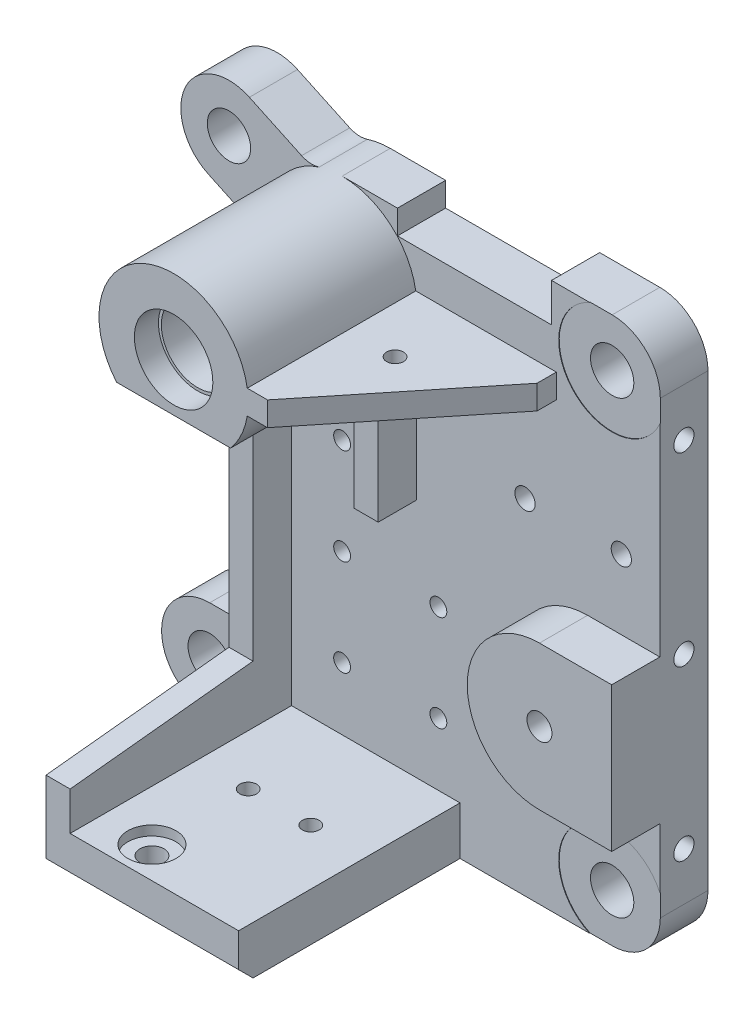
SolidWorks part; units mm, degrees
material "3D printed plastic"
ref_plane "Front Plane" through (0, 0, 0) normal (0, 0, 1) x (1, 0, 0)
ref_plane "Top Plane" through (0, 0, 0) normal (0, 1, 0) x (1, 0, 0)
ref_plane "Right Plane" through (0, 0, 0) normal (1, 0, 0) x (0, 0, -1)
sketch "Sketch1" plane through (0, 0, 0) normal (1, 0, 0) x (0, 0, -1)
  line L0 (0, 15.5) -> (-45, 15.5)
  line L1 (-45, 15.5) -> (-45, 8.15)
  line L2 (-45, 8.15) -> (-40, 8.15)
  line L3 (-40, 8.15) -> (-40, 7.55)
  line L4 (-40, 7.55) -> (-5, 7.55)
  line L5 (-5, 7.55) -> (-5, 8.15)
  line L6 (-5, 8.15) -> (0, 8.15)
  line L7 (0, 8.15) -> (0, 15.5)
  line L8 (0, 0) -> (-45, 0) construction
  dimension "D1" = 16.3
  dimension "D2" = 5
  dimension "D3" = 0.6
  dimension "D4" = 45
  dimension "D5" = 31
revolve "Revolve1" add sketch "Sketch1" angle 360 about L8
sketch "Sketch2" plane through (0, 0, 0) normal (0, 0, 1) x (1, 0, 0)
  line L0 (0, 15.5) -> (66, 15.5)
  line L1 (66, 15.5) -> (66, -95)
  line L2 (66, -95) -> (-15.5, -95)
  line L3 (-15.5, -95) -> (-15.5, 0)
  line L4 (0, 0) -> (0, -53) construction
  line L5 (0, -53) -> (51, -53) construction
  arc A0 (-15.5, 0) -> (0, 15.5) centre (0, 0) ccw
  circle A1 centre (0, 0) radius 15.5 construction
  dimension "D1" = 66
  dimension "D2" = 95
  dimension "D3" = 53
  dimension "D4" = 51
extrude "Boss-Extrude1" add sketch "Sketch2" along normal blind 10
ref_axis "Axis1" through (51, -53, 0) along (0, 0, 1)
sketch "Sketch3" plane through (0, 0, 10) normal (0, 0, 1) x (1, 0, 0)
  line L0 (51, -38) -> (66, -38)
  line L1 (66, -95) -> (66, 15.5) construction
  line L2 (66, -38) -> (66, -68)
  line L3 (66, -68) -> (51, -68)
  circle A0 centre (51, -53) radius 2.6
  arc A1 (51, -38) -> (51, -68) centre (51, -53) ccw
  dimension "D1" = 5.2
extrude "Boss-Extrude2" add sketch "Sketch3" along normal blind 10
sketch "Sketch4" plane through (0, 0, 10) normal (0, 0, 1) x (1, 0, 0)
  line L1 (51, -57.6765) -> (55.05, -55.3383)
  line L2 (55.05, -55.3383) -> (55.05, -50.6617)
  line L3 (55.05, -50.6617) -> (51, -48.3235)
  line L4 (51, -48.3235) -> (46.95, -50.6617)
  line L5 (46.95, -50.6617) -> (46.95, -55.3383)
  line L6 (46.95, -55.3383) -> (51, -57.6765)
  circle A0 centre (51, -53) radius 4.05 construction
  dimension "D1" = 8.1
extrude "Cut-Extrude1" cut sketch "Sketch4" against normal through all
sketch "Sketch5" plane through (0, -95, 0) normal (0, -1, 0) x (1, 0, 0)
  line L0 (-15.5, 0) -> (66, 0) construction
  line L1 (-15.5, 10) -> (24.5, 10)
  line L2 (-15.5, 10) -> (-15.5, 56)
  line L3 (-15.5, 56) -> (24.5, 56)
  line L4 (24.5, 10) -> (24.5, 56)
  dimension "D1" = 56
  dimension "D2" = 40
extrude "Boss-Extrude3" add sketch "Sketch5" against normal blind 10
sketch "Sketch6" plane through (0, -85, 0) normal (0, 1, 0) x (1, 0, 0)
  line L0 (-15.5, 0) -> (66, 0) construction
  circle A0 centre (0, -49.5) radius 2.5
  dimension "D1" = 5
  dimension "D3" = 0
  dimension "D2" = 49.5
extrude "Cut-Extrude2" cut sketch "Sketch6" against normal through all
sketch "Sketch7" plane through (0, -85, 0) normal (0, 1, 0) x (1, 0, 0)
  circle A0 centre (0, -49.5) radius 5
  dimension "D1" = 10
extrude "Cut-Extrude3" cut sketch "Sketch7" against normal blind 2
sketch "Sketch8" plane through (-15.5, 0, 0) normal (-1, 0, 0) x (0, 0, 1)
  line L0 (56, -85) -> (56, -77)
  line L1 (56, -77) -> (18, -73)
  line L2 (10, 0) -> (18, 0)
  line L3 (18, 0) -> (18, -73)
  line L4 (10, 0) -> (10, -85) construction
  line L5 (10, 0) -> (10, -85)
  line L6 (10, -85) -> (56, -85)
  dimension "D1" = 8
  dimension "D2" = 8
  dimension "D3" = 12
extrude "Boss-Extrude4" add sketch "Sketch8" against normal blind 5
sketch "Sketch9" plane through (0, 0, 45) normal (0, 0, 1) x (1, 0, 0)
  line L1 (-11.8427, -10) -> (11.8427, -10)
  line L2 (-11.8427, -10) -> (-11.8427, -15.5)
  line L3 (-11.8427, -15.5) -> (11.8427, -15.5)
  line L4 (11.8427, -10) -> (11.8427, -15.5)
  circle A0 centre (0, 0) radius 15.5 construction
  arc A1 (-10.5, -11.4018) -> (0, 15.5) centre (0, 0) ccw construction
  dimension "D1" = 10
extrude "Cut-Extrude4" cut sketch "Sketch9" against normal up to surface (27 mm away) up to face at (-13.2988, -39.4815, 18)
sketch "Sketch10" plane through (0, 0, 10) normal (0, 0, 1) x (1, 0, 0)
  line L0 (66, 15.5) -> (0, 15.5) construction
  line L1 (11.5, 15.5) -> (43.5, 15.5)
  line L2 (11.5, 15.5) -> (11.5, 10.5)
  line L3 (11.5, 10.5) -> (43.5, 10.5)
  line L4 (43.5, 15.5) -> (43.5, 10.5)
  line L5 (-15.5, -73) -> (-15.5, 0) construction
  dimension "D1" = 5
  dimension "D2" = 32
  dimension "D3" = 27
extrude "Cut-Extrude5" cut sketch "Sketch10" against normal through all
other "Move Face1" face at (54.75, 15.5, 5) offset 3 parameters "D1"=3
sketch "Sketch11" plane through (0, 0, 18) normal (0, 0, 1) x (1, 0, 0)
  line L1 (15.5, 0) -> (10.5, 0)
  line L2 (15.5, 0) -> (15.5, -35)
  line L3 (15.5, -35) -> (10.5, -35)
  line L4 (10.5, 0) -> (10.5, -35)
  line L5 (10.5, 0) -> (0, 0) construction
  line L6 (11.8427, -10) -> (-11.8427, -10) construction
  arc A0 (11.8427, -10) -> (-11.8427, -10) centre (0, 0) ccw construction
  arc A1 (-10.5, -11.4018) -> (0, 15.5) centre (0, 0) ccw construction
  dimension "D1" = 5
  dimension "D2" = 25
extrude "Boss-Extrude5" add sketch "Sketch11" against normal up to next
sketch "Sketch12" plane through (0, 0, 0) normal (0, 0, 1) x (1, 0, 0)
  line L0 (-6.4864, 14.0775) -> (-19.2606, 20.0569)
  line L1 (-27.7394, 1.9431) -> (-14.9652, -4.0363)
  line L2 (0, 0) -> (-23.5, 11) construction
  line L3 (-15.5, -73) -> (-15.5, 0) construction
  line L4 (-15.5, -95) -> (-27.5, -95)
  line L5 (-27.5, -75) -> (-15.5, -75)
  line L6 (-15.5, -75) -> (-15.5, -95)
  line L7 (-27.5, -85) -> (-27.5, 11) construction
  line L8 (-27.5, 11) -> (-23.5, 11) construction
  arc A0 (-6.4864, 14.0775) -> (-14.9652, -4.0363) centre (0, 0) ccw
  arc A1 (-19.2606, 20.0569) -> (-27.7394, 1.9431) centre (-23.5, 11) ccw
  arc A2 (11.8427, -10) -> (-11.8427, -10) centre (0, 0) ccw construction
  arc A3 (-27.5, -95) -> (-27.5, -75) centre (-27.5, -85) cw
  dimension "D1" = 4
  dimension "D4" = 12
  dimension "D2" = 96
  dimension "D3" = 20
extrude "Boss-Extrude6" add sketch "Sketch12" along normal up to surface (10 mm away) up to face at (28.6426, -30.3522, 10)
fillet "Fillet1" radius 5 5 edges at (-10.5, -11.4018, 14) (10.5, -11.4018, 14) (-6.4864, 14.0775, 5) (-15.5, -3.786, 5) (-15.5, -75, 5)
sketch "Sketch13" plane through (0, 0, 0) normal (0, 0, -1) x (-1, 0, 0)
  line L0 (-56, 8.5) -> (-56, -85) construction
  line L1 (-66, -38) -> (-66, 18.5) construction
  line L2 (-66, 18.5) -> (-43.5, 18.5) construction
  line L3 (-24.5, -95) -> (-66, -95) construction
  circle A0 centre (23.5, 11) radius 4.5
  circle A1 centre (-56, 8.5) radius 4.5
  circle A2 centre (27.5, -85) radius 4.5
  circle A3 centre (-56, -85) radius 4.5
  dimension "D1" = 9
  dimension "D2" = 10
  dimension "D4" = 10
  dimension "D3" = 10
extrude "Cut-Extrude6" cut sketch "Sketch13" against normal through all
fillet "Fillet2" radius 10 2 edges at (66, -95, 5) (66, 18.5, 5)
sketch "Sketch14" plane through (0, 0, 0) normal (0, 1, 0) x (1, 0, 0)
  line L0 (15.5, -45) -> (19.5, -45)
  line L1 (15.5, -45) -> (15.5, -18) construction
  line L2 (19.5, -45) -> (44.5, -14)
  line L3 (44.5, -14) -> (44.5, -10)
  line L4 (11.5, -10) -> (43.5, -10) construction
  line L5 (44.5, -10) -> (14.5, -10)
  line L6 (14.5, -10) -> (14.5, -45)
  line L7 (14.5, -45) -> (15.5, -45)
  dimension "D1" = 1
  dimension "D2" = 35
  dimension "D3" = 30
  dimension "D4" = 4
extrude "Boss-Extrude7" add sketch "Sketch14" along normal mid plane 5
chamfer "Chamfer1" distance 3 angle 45 1 edges at (4.5, -95, 56)
sketch "Sketch15" plane through (0, 0, 10) normal (0, 0, 1) x (1, 0, 0)
  circle A0 centre (56, 8.5) radius 11
  circle A1 centre (56, -85) radius 11
  arc A2 (56, -95) -> (66, -85) centre (56, -85) ccw construction
  arc A3 (66, 8.5) -> (56, 18.5) centre (56, 8.5) ccw construction
  dimension "D1" = 1
  dimension "D2" = 1
extrude "Cut-Extrude7" cut sketch "Sketch15" against normal blind 0.1
sketch "Sketch18" plane through (66, 0, 0) normal (1, 0, 0) x (0, 0, -1)
  line L0 (-5, -1.5) -> (-5, 18.5) construction
  line L1 (-9.9, 18.5) -> (0, 18.5) construction
  line L2 (-5, -75) -> (-5, -95) construction
  line L6 (-9.9, -85) -> (0, -85) construction
  line L9 (-10, -95) -> (0, -95) construction
  line L11 (-5, -40) -> (-5, -75) construction
  circle A0 centre (-5, -75) radius 2.1
  circle A1 centre (-5, -1.5) radius 2.1
  circle A2 centre (-5, -40) radius 2.1
  dimension "D1" = 10
  dimension "D2" = 4.2
  dimension "D3" = 35
extrude "Cut-Extrude10" cut sketch "Sketch18" against normal blind 20
sketch "Sketch19" plane through (66, 0, 0) normal (1, 0, 0) x (0, 0, -1)
  line L0 (-2.9504, 2.05) -> (0, 2.05)
  line L1 (-0.9008, -1.5) -> (-2.9504, 2.05) construction
  line L2 (-2.9504, 2.05) -> (-7.0496, 2.05)
  line L3 (-7.0496, 2.05) -> (-9.0992, -1.5)
  line L4 (-9.0992, -1.5) -> (-7.0496, -5.05)
  line L5 (-7.0496, -5.05) -> (-2.9504, -5.05)
  line L6 (-2.9504, -5.05) -> (-0.9008, -1.5) construction
  line L7 (-0.9008, -75) -> (-2.9504, -71.45) construction
  line L8 (-2.9504, -71.45) -> (-7.0496, -71.45)
  line L9 (-7.0496, -71.45) -> (-9.0992, -75)
  line L10 (-9.0992, -75) -> (-7.0496, -78.55)
  line L11 (-7.0496, -78.55) -> (-2.9504, -78.55)
  line L12 (-2.9504, -78.55) -> (-0.9008, -75) construction
  line L13 (0, -85) -> (0, 8.5) construction
  line L14 (0, 2.05) -> (0, -5.05)
  line L15 (0, -5.05) -> (-2.9504, -5.05)
  line L16 (-2.9504, -71.45) -> (0, -71.45)
  line L17 (0, -71.45) -> (0, -78.55)
  line L18 (0, -78.55) -> (-2.9504, -78.55)
  line L19 (0, -57.5) -> (-13.2804, -57.5) construction
  line L20 (-2.9504, -36.45) -> (-0.9008, -40) construction
  line L21 (-0.9008, -40) -> (-2.9504, -43.55) construction
  line L22 (0, -36.45) -> (-2.9504, -36.45)
  line L23 (0, -43.55) -> (0, -36.45)
  line L24 (-2.9504, -43.55) -> (0, -43.55)
  line L25 (-7.0496, -36.45) -> (-2.9504, -36.45)
  line L26 (-9.0992, -40) -> (-7.0496, -36.45)
  line L27 (-7.0496, -43.55) -> (-9.0992, -40)
  line L28 (-2.9504, -43.55) -> (-7.0496, -43.55)
  circle A0 centre (-5, -1.5) radius 3.55 construction
  circle A1 centre (-5, -75) radius 3.55 construction
  circle A2 centre (-5, -40) radius 3.55 construction
  dimension "D1" = 7.1
extrude "Cut-Extrude11" cut sketch "Sketch19" against normal blind 5.5 from offset 4 offset against normal yes
sketch "Sketch20" plane through (0, -95, 0) normal (0, -1, 0) x (1, 0, 0)
  line L0 (-27.5, 5) -> (-17.5, 5) construction
  line L1 (-27.5, 10) -> (-27.5, 0) construction
  line L2 (56, 4.95) -> (41, 4.95) construction
  line L3 (56, 0) -> (56, 9.9) construction
  circle A0 centre (-17.5, 5) radius 2.1
  circle A1 centre (41, 4.95) radius 2.1
  dimension "D1" = 10
  dimension "D2" = 4.2
  dimension "D3" = 15
extrude "Cut-Extrude12" cut sketch "Sketch20" against normal blind 16
sketch "Sketch21" plane through (0, -95, 0) normal (0, -1, 0) x (1, 0, 0)
  line L0 (-21.05, 2.9504) -> (-21.05, 0)
  line L1 (-17.5, 0.9008) -> (-13.95, 2.9504) construction
  line L2 (-13.95, 2.9504) -> (-13.95, 7.0496)
  line L3 (-13.95, 7.0496) -> (-17.5, 9.0992)
  line L4 (-17.5, 9.0992) -> (-21.05, 7.0496)
  line L5 (-21.05, 7.0496) -> (-21.05, 2.9504)
  line L6 (-21.05, 2.9504) -> (-17.5, 0.9008) construction
  line L7 (41, 0.8508) -> (44.55, 2.9004) construction
  line L8 (44.55, 2.9004) -> (44.55, 6.9996)
  line L9 (44.55, 6.9996) -> (41, 9.0492)
  line L10 (41, 9.0492) -> (37.45, 6.9996)
  line L11 (37.45, 6.9996) -> (37.45, 2.9004)
  line L12 (37.45, 2.9004) -> (41, 0.8508) construction
  line L13 (-21.05, 0) -> (-13.95, 0)
  line L14 (-27.5, 0) -> (56, 0) construction
  line L15 (-13.95, 0) -> (-13.95, 2.9504)
  line L16 (37.45, 2.9004) -> (37.45, 0)
  line L17 (37.45, 0) -> (44.55, 0)
  line L18 (44.55, 0) -> (44.55, 2.9004)
  line L19 (44.55, 2.9004) -> (49.6379, 2.9637)
  circle A0 centre (-17.5, 5) radius 3.55 construction
  circle A1 centre (41, 4.95) radius 3.55 construction
  circle M1 centre (41, 4.95) radius 2.1
  circle M2 centre (-17.5, 5) radius 2.1
  line M12 (-27.5, 0) -> (56, 0)
  dimension "D1" = 7.1
extrude "Cut-Extrude13" cut sketch "Sketch21" against normal blind 5.5 from offset 4 contours L15 L2 L3 L4 L5 L0 M12 M2 | L18 L8 L9 L10 L11 L16 M12 M1 region at (-20.9346, -95, 5) region at (37.565, -95, 1.4502) offset against normal yes
other "Move Face2" flip direction yes face at (46, -37.9, 5) offset 5 parameters "D1"=5
fillet "Fillet3" radius 5 1 edges at (0, -10, 18)
sketch "Sketch22" plane through (0, 0, 10) normal (0, 0, 1) x (1, 0, 0)
  line L0 (58, -23.5) -> (38, -23.5) construction
  line L1 (66, -38) -> (66, 3.9174) construction
  circle A0 centre (58, -23.5) radius 2.1
  circle A1 centre (38, -23.5) radius 2.1
  circle A3 centre (0, 0) radius 8.15 construction
  dimension "D1" = 20
  dimension "D2" = 4.2
  dimension "D3" = 8
  dimension "D4" = 23.5
extrude "Cut-Extrude14" cut sketch "Sketch22" against normal through all
sketch "Sketch23" plane through (0, 0, 10) normal (0, 0, 1) x (1, 0, 0)
  line L1 (38, -27.5992) -> (41.55, -25.5496)
  line L2 (41.55, -25.5496) -> (41.55, -21.4504)
  line L3 (41.55, -21.4504) -> (38, -19.4008)
  line L4 (38, -19.4008) -> (34.45, -21.4504)
  line L5 (34.45, -21.4504) -> (34.45, -25.5496)
  line L6 (34.45, -25.5496) -> (38, -27.5992)
  line L7 (58, -27.5992) -> (61.55, -25.5496)
  line L8 (61.55, -25.5496) -> (61.55, -21.4504)
  line L9 (61.55, -21.4504) -> (58, -19.4008)
  line L10 (58, -19.4008) -> (54.45, -21.4504)
  line L11 (54.45, -21.4504) -> (54.45, -25.5496)
  line L12 (54.45, -25.5496) -> (58, -27.5992)
  circle A0 centre (38, -23.5) radius 3.55 construction
  circle A1 centre (58, -23.5) radius 3.55 construction
  dimension "D1" = 7.1
extrude "Cut-Extrude15" cut sketch "Sketch23" against normal through all from offset 4 offset against normal yes
sketch "Sketch24" plane through (0, 0, 10) normal (0, 0, 1) x (1, 0, 0)
  line L0 (0, -32) -> (0, -52) construction
  line L1 (0, -52) -> (0, -72) construction
  line L2 (0, -72) -> (20, -72) construction
  line L3 (20, -72) -> (20, -52) construction
  line L4 (20, -52) -> (0, -52) construction
  line L5 (0, -32) -> (0, 0) construction
  line L6 (40, -72) -> (20, -72) construction
  circle A0 centre (0, -32) radius 1.75
  circle A1 centre (0, -52) radius 1.75
  circle A2 centre (0, -72) radius 1.75
  circle A3 centre (20, -72) radius 1.75
  circle A4 centre (20, -52) radius 1.75
  circle A5 centre (40, -72) radius 1.75
  dimension "D1" = 20
  dimension "D3" = 3.5
  dimension "D2" = 32
extrude "Cut-Extrude16" cut sketch "Sketch24" against normal through all
sketch "Sketch25" plane through (0, -85, 0) normal (0, 1, 0) x (1, 0, 0)
  line L0 (13, -29.5) -> (0, -29.5) construction
  line L1 (0, -29.5) -> (0, -49.5) construction
  circle A0 centre (0, -29.5) radius 1.75
  circle A1 centre (13, -29.5) radius 1.75
  dimension "D1" = 20
  dimension "D3" = 3.5
  dimension "D2" = 13
extrude "Cut-Extrude17" cut sketch "Sketch25" against normal up to next
sketch "Sketch26" plane through (0, 2.5, 0) normal (0, 1, 0) x (1, 0, 0)
  line L1 (11.5, 0) -> (43.5, 0) construction
  circle A0 centre (25, -24) radius 1.75
  dimension "D1" = 3.5
  dimension "D2" = 25
  dimension "D3" = 24
extrude "Cut-Extrude18" cut sketch "Sketch26" against normal up to next
